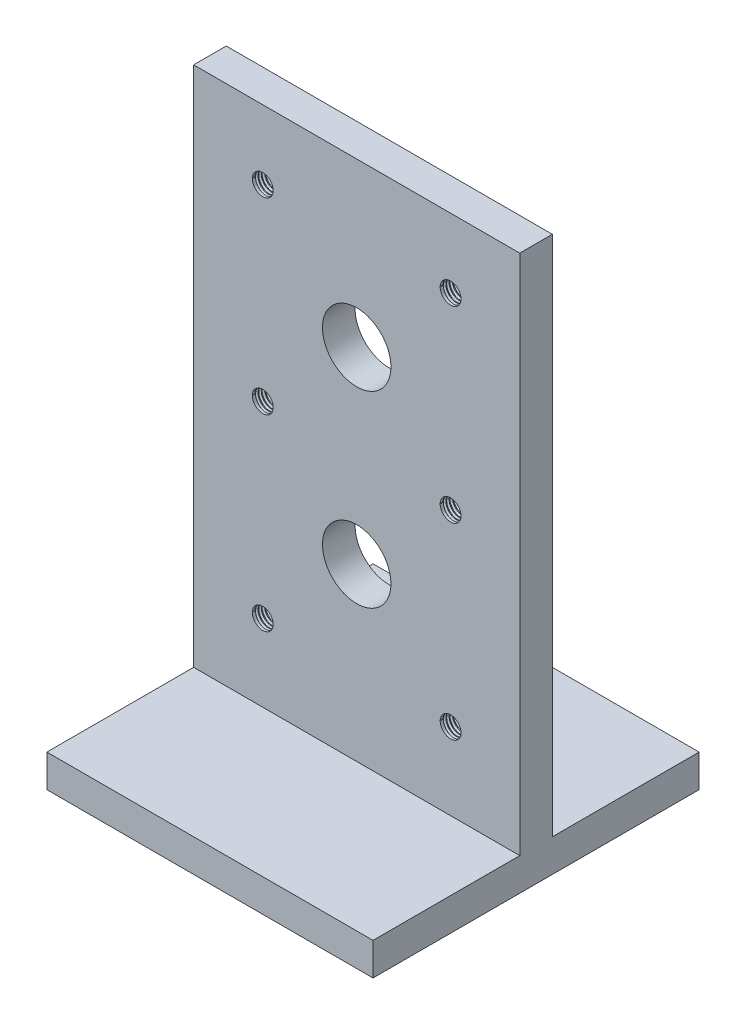
SolidWorks part; units mm, degrees
ref_plane "前视基准面" through (0, 0, 0) normal (0, 0, 1) x (1, 0, 0)
ref_plane "上视基准面" through (0, 0, 0) normal (0, 1, 0) x (1, 0, 0)
ref_plane "右视基准面" through (0, 0, 0) normal (1, 0, 0) x (0, 0, -1)
other "Configuration Table"
sketch "Sketch1" plane through (0, 0, 0) normal (0, 0, 1) x (1, 0, 0)
  line L1 (0, 0) -> (50, 0)
  line L2 (0, 0) -> (0, 5)
  line L3 (0, 5) -> (50, 5)
  line L4 (50, 0) -> (50, 5)
  dimension "D1" = 5
  dimension "D2" = 50
extrude "Boss-Extrude1" add sketch "Sketch1" along normal blind 50
sketch "Sketch2" plane through (0, 5, 0) normal (0, 1, 0) x (1, 0, 0)
  line L0 (0, -50) -> (0, 0) construction
  line L1 (0, -22.5) -> (50, -22.5)
  line L2 (0, -22.5) -> (0, -27.5)
  line L3 (0, -27.5) -> (50, -27.5)
  line L4 (50, -22.5) -> (50, -27.5)
  line L5 (50, -50) -> (50, 0) construction
  line L6 (50, 0) -> (0, 0) construction
  dimension "D1" = 5
  dimension "D2" = 22.5
extrude "Boss-Extrude2" add sketch "Sketch2" along normal blind 80
sketch "Sketch3" plane through (0, 0, 27.5) normal (0, 0, 1) x (1, 0, 0)
  line L0 (25, 40) -> (25, 10) construction
  line L1 (5, 80) -> (45, 80)
  line L2 (5, 80) -> (5, 40)
  line L3 (5, 40) -> (45, 40)
  line L4 (45, 80) -> (45, 40)
  line L5 (0, 85) -> (50, 85) construction
  line L6 (0, 85) -> (0, 5) construction
  line L7 (25, 80) -> (25, 40) construction
  line L8 (5, 60) -> (45, 60) construction
  line L9 (5, 40) -> (45, 40)
  line L10 (5, 40) -> (5, 10)
  line L11 (5, 10) -> (45, 10)
  line L12 (45, 40) -> (45, 10)
  line L13 (5, 31.2) -> (45, 31.2) construction
  circle A0 centre (10.6, 74.4) radius 1.6
  circle A1 centre (10.6, 45.6) radius 1.6
  circle A2 centre (39.4, 74.4) radius 1.6
  circle A3 centre (39.4, 45.6) radius 1.6
  circle A4 centre (25, 60) radius 5.25
  circle A5 centre (10.6, 16.8) radius 1.6
  circle A6 centre (39.4, 16.8) radius 1.6
  circle A7 centre (25, 31.2) radius 5.25
  dimension "D5" = 3.2
  dimension "D6" = 3.2
  dimension "D7" = 28.8
  dimension "D8" = 5.6
  dimension "D9" = 5.6
  dimension "D10" = 5.6
  dimension "D11" = 3.2
  dimension "D12" = 5.6
  dimension "D13" = 3.2
  dimension "D14" = 5.6
  dimension "D15" = 28.8
  dimension "D16" = 5.6
  dimension "D17" = 10.5
  dimension "D19" = 28.8
  dimension "D20" = 3.2
  dimension "D21" = 3.2
  dimension "D22" = 28.8
  dimension "D23" = 6.8
  dimension "D24" = 6.8
  dimension "D25" = 14.4
  dimension "D26" = 10.5
  dimension "D1" = 40
  dimension "D2" = 40
  dimension "D3" = 5
  dimension "D4" = 5
  dimension "D18" = 30
extrude "Cut-Extrude2" cut sketch "Sketch3" against normal blind 50 contours A0 | A2 | A1 | A3 | A4 | A5 | A6 | A7
thread "Thread1" pitch 0.5 method cut profile "Thread Profile1" start angle 0, offset 0, length 0, pitch 0.5, diameter 3.2
ref_plane "Plane1" through (9, 74.4, 27.5) normal (0, -1, 0) x (-1, 0, 0)
sketch "Thread Profile1" plane through (9, 74.4, 27.5) normal (0, -1, 0) x (-1, 0, 0)
  line L0 (0, 0) -> (0, 0.5) construction
  line L1 (0, 0) -> (0.2706, 0.1562)
  line L2 (0.2706, 0.1562) -> (0.2706, 0.2187)
  line L3 (0.2706, 0.2187) -> (0, 0.375)
  line L4 (0.2706, 0.1875) -> (0, 0.1875) construction
  line L11 (0, 0) -> (0, 0.375)
  point P2 (0, 0)
  dimension "Pitch" = 0.5
  dimension "Profile_Angle" = 60
  dimension "Profile_Land" = 0.0625
  dimension "Profile_Height" = 0.2706
thread "Thread2" pitch 0.5 method cut profile "Thread Profile2" start angle 0, offset 0, length 0, pitch 0.5, diameter 3.2
ref_plane "Plane2" through (37.8, 74.4, 27.5) normal (0, -1, 0) x (-1, 0, 0)
sketch "Thread Profile2" plane through (37.8, 74.4, 27.5) normal (0, -1, 0) x (-1, 0, 0)
  line L0 (0, 0) -> (0, 0.5) construction
  line L1 (0, 0) -> (0.2706, 0.1562)
  line L2 (0.2706, 0.1562) -> (0.2706, 0.2187)
  line L3 (0.2706, 0.2187) -> (0, 0.375)
  line L4 (0.2706, 0.1875) -> (0, 0.1875) construction
  line L11 (0, 0) -> (0, 0.375)
  point P2 (0, 0)
  dimension "Pitch" = 0.5
  dimension "Profile_Angle" = 60
  dimension "Profile_Land" = 0.0625
  dimension "Profile_Height" = 0.2706
thread "Thread3" pitch 0.5 method cut profile "Thread Profile3" start angle 0, offset 0, length 0, pitch 0.5, diameter 3.2
ref_plane "Plane3" through (9, 45.6, 27.5) normal (0, -1, 0) x (-1, 0, 0)
sketch "Thread Profile3" plane through (9, 45.6, 27.5) normal (0, -1, 0) x (-1, 0, 0)
  line L0 (0, 0) -> (0, 0.5) construction
  line L1 (0, 0) -> (0.2706, 0.1562)
  line L2 (0.2706, 0.1562) -> (0.2706, 0.2187)
  line L3 (0.2706, 0.2187) -> (0, 0.375)
  line L4 (0.2706, 0.1875) -> (0, 0.1875) construction
  line L11 (0, 0) -> (0, 0.375)
  point P2 (0, 0)
  dimension "Pitch" = 0.5
  dimension "Profile_Angle" = 60
  dimension "Profile_Land" = 0.0625
  dimension "Profile_Height" = 0.2706
thread "Thread4" pitch 0.5 method cut profile "Thread Profile4" start angle 0, offset 0, length 0, pitch 0.5, diameter 3.2
ref_plane "Plane4" through (37.8, 45.6, 27.5) normal (0, -1, 0) x (-1, 0, 0)
sketch "Thread Profile4" plane through (37.8, 45.6, 27.5) normal (0, -1, 0) x (-1, 0, 0)
  line L0 (0, 0) -> (0, 0.5) construction
  line L1 (0, 0) -> (0.2706, 0.1562)
  line L2 (0.2706, 0.1562) -> (0.2706, 0.2187)
  line L3 (0.2706, 0.2187) -> (0, 0.375)
  line L4 (0.2706, 0.1875) -> (0, 0.1875) construction
  line L11 (0, 0) -> (0, 0.375)
  point P2 (0, 0)
  dimension "Pitch" = 0.5
  dimension "Profile_Angle" = 60
  dimension "Profile_Land" = 0.0625
  dimension "Profile_Height" = 0.2706
thread "Thread5" pitch 0.5 method cut profile "Thread Profile5" start angle 0, offset 0, length 0, pitch 0.5, diameter 3.2
ref_plane "Plane5" through (9, 16.8, 27.5) normal (0, -1, 0) x (-1, 0, 0)
sketch "Thread Profile5" plane through (9, 16.8, 27.5) normal (0, -1, 0) x (-1, 0, 0)
  line L0 (0, 0) -> (0, 0.5) construction
  line L1 (0, 0) -> (0.2706, 0.1562)
  line L2 (0.2706, 0.1562) -> (0.2706, 0.2187)
  line L3 (0.2706, 0.2187) -> (0, 0.375)
  line L4 (0.2706, 0.1875) -> (0, 0.1875) construction
  line L11 (0, 0) -> (0, 0.375)
  point P2 (0, 0)
  dimension "Pitch" = 0.5
  dimension "Profile_Angle" = 60
  dimension "Profile_Land" = 0.0625
  dimension "Profile_Height" = 0.2706
thread "Thread6" pitch 0.5 method cut profile "Thread Profile6" start angle 0, offset 0, length 0, pitch 0.5, diameter 3.2
ref_plane "Plane6" through (37.8, 16.8, 27.5) normal (0, -1, 0) x (-1, 0, 0)
sketch "Thread Profile6" plane through (37.8, 16.8, 27.5) normal (0, -1, 0) x (-1, 0, 0)
  line L0 (0, 0) -> (0, 0.5) construction
  line L1 (0, 0) -> (0.2706, 0.1562)
  line L2 (0.2706, 0.1562) -> (0.2706, 0.2187)
  line L3 (0.2706, 0.2187) -> (0, 0.375)
  line L4 (0.2706, 0.1875) -> (0, 0.1875) construction
  line L11 (0, 0) -> (0, 0.375)
  point P2 (0, 0)
  dimension "Pitch" = 0.5
  dimension "Profile_Angle" = 60
  dimension "Profile_Land" = 0.0625
  dimension "Profile_Height" = 0.2706
